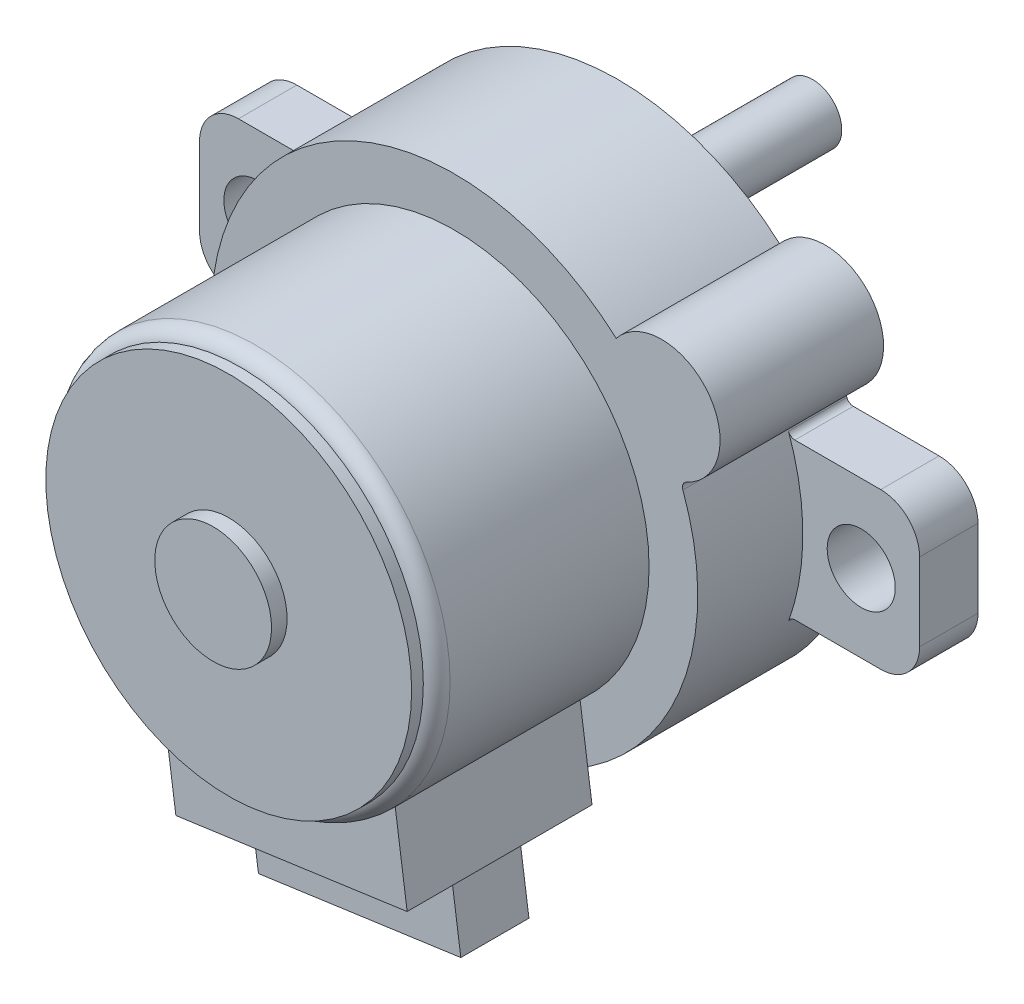
SolidWorks part; units mm, degrees
ref_plane "正面" through (0, 0, 0) normal (0, 0, 1) x (1, 0, 0)
ref_plane "平面" through (0, 0, 0) normal (0, 1, 0) x (1, 0, 0)
ref_plane "右側面" through (0, 0, 0) normal (1, 0, 0) x (0, 0, -1)
sketch "ｽｹｯﾁ1" plane through (0, 0, 0) normal (0, 0, 1) x (1, 0, 0)
  circle A0 centre (0, 0) radius 10
  dimension "D1" = 20
extrude "ﾎﾞｽ - 押し出し1" add sketch "ｽｹｯﾁ1" along normal blind 11.6
sketch "ｽｹｯﾁ2" plane through (0, 0, 0) normal (0, 0, 1) x (1, 0, 0)
  circle A0 centre (0, 0) radius 12.5
  dimension "D1" = 25
extrude "ﾎﾞｽ - 押し出し2" add sketch "ｽｹｯﾁ2" against normal blind 8.4
sketch "ｽｹｯﾁ3" plane through (0, 0, -8.4) normal (0, 0, -1) x (-1, 0, 0)
  line L0 (-28.5789, 0) -> (34.8787, 0) construction
  line L1 (-18.5, 2) -> (-18.5, -2)
  line L2 (-16.5, -4) -> (-11.8427, -4)
  line L3 (-16.5, 4) -> (-11.8427, 4)
  line L4 (0, 0) -> (-18.1375, 12.7) construction
  line L5 (16.5, 4) -> (11.8427, 4)
  line L6 (16.5, -4) -> (11.8427, -4)
  line L7 (18.5, -2) -> (18.5, 2)
  circle A0 centre (-15.5, 0) radius 1.75
  circle A1 centre (0, 0) radius 12.5
  arc A2 (-8.3112, 9.3367) -> (-11.6162, 4.6167) centre (0, 0) ccw
  arc A3 (-8.3112, 9.3367) -> (-11.6162, 4.6167) centre (-10.649, 7.4565) ccw
  arc A4 (-18.5, -2) -> (-16.5, -4) centre (-16.5, -2) ccw
  arc A5 (-18.5, 2) -> (-16.5, 4) centre (-16.5, 2) cw
  arc A6 (-11.8427, 4) -> (-11.8427, -4) centre (0, 0) ccw
  arc A8 (8.3112, -9.3367) -> (11.6162, -4.6167) centre (0, 0) ccw
  arc A9 (8.3112, -9.3367) -> (11.6162, -4.6167) centre (10.649, -7.4565) ccw
  arc A10 (11.8427, -4) -> (11.8427, 4) centre (0, 0) ccw
  arc A11 (18.5, -2) -> (16.5, -4) centre (16.5, -2) cw
  arc A12 (18.5, 2) -> (16.5, 4) centre (16.5, 2) ccw
  circle A13 centre (15.5, 0) radius 1.75
  point P8 (-18.5, 0)
  point P18 (-18.5, -4)
  point P21 (-18.5, 4)
  point P39 (0, 0)
  dimension "D4" = 3.5
  dimension "D5" = 15.5
  dimension "D7" = 6
  dimension "D9" = 2
  dimension "D2" = 8
  dimension "D3" = 18.5
  dimension "D6" = 35
  dimension "D8" = 13
  dimension "D1" = 0
  dimension "D10" = 2
extrude "ﾎﾞｽ - 押し出し3" add sketch "ｽｹｯﾁ3" against normal blind 3
sketch "ｽｹｯﾁ4" plane through (0, 0, -5.4) normal (0, 0, 1) x (1, 0, 0)
  arc A0 (-11.6162, -4.6167) -> (-8.3112, -9.3367) centre (-10.649, -7.4565) ccw construction
  arc A1 (-11.6162, -4.6167) -> (-8.3112, -9.3367) centre (0, 0) ccw construction
  arc A2 (11.6162, 4.6167) -> (8.3112, 9.3367) centre (10.649, 7.4565) ccw construction
  arc A3 (11.6162, 4.6167) -> (8.3112, 9.3367) centre (0, 0) ccw construction
  arc A4 (-11.6162, -4.6167) -> (-8.3112, -9.3367) centre (-10.649, -7.4565) ccw
  arc A5 (-11.6162, -4.6167) -> (-8.3112, -9.3367) centre (0, 0) ccw
  arc A6 (11.6162, 4.6167) -> (8.3112, 9.3367) centre (10.649, 7.4565) ccw
  arc A7 (11.6162, 4.6167) -> (8.3112, 9.3367) centre (0, 0) ccw
extrude "ﾎﾞｽ - 押し出し4" add sketch "ｽｹｯﾁ4" along normal up to surface (5.4 mm away) up to face at (10, 0, 0)
sketch "ｽｹｯﾁ5" plane through (0, 0, -8.4) normal (0, 0, -1) x (-1, 0, 0)
  line L0 (0, 6) -> (0, 0) construction
  circle A0 centre (0, 6) radius 3
  dimension "D1" = 6
  dimension "D2" = 6
extrude "ﾎﾞｽ - 押し出し5" add sketch "ｽｹｯﾁ5" along normal blind 2
sketch "ｽｹｯﾁ6" plane through (0, 0, -10.4) normal (0, 0, -1) x (-1, 0, 0)
  circle A0 centre (0, 6) radius 1.5
  dimension "D1" = 3
extrude "ﾎﾞｽ - 押し出し6" add sketch "ｽｹｯﾁ6" along normal blind 8
sketch "ｽｹｯﾁ7" plane through (0, 0, 11.6) normal (0, 0, 1) x (1, 0, 0)
  circle A0 centre (0, 0) radius 3
  dimension "D1" = 6
extrude "ﾎﾞｽ - 押し出し7" add sketch "ｽｹｯﾁ7" along normal blind 0.8
sketch "ｽｹｯﾁ8" plane through (0, 0, 11.6) normal (0, 0, 1) x (1, 0, 0)
  line L0 (0, 0) -> (2.4461, -17.4049) construction
  line L1 (0, 0) -> (0, -16.419) construction
  line L2 (-4.2159, -13.1144) -> (7.6674, -11.4443)
  line L3 (7.6674, -11.4443) -> (7.055, -7.0871)
  line L4 (-4.8282, -8.7572) -> (-4.2159, -13.1144)
  circle A0 centre (0, 0) radius 3 construction
  circle A1 centre (0, 0) radius 10
  arc A2 (-4.8282, -8.7572) -> (7.055, -7.0871) centre (0, 0) ccw
  point P9 (1.7257, -12.2793)
  dimension "D2" = 8
  dimension "D3" = 12
  dimension "D4" = 12.4
  dimension "D1" = 0
extrude "ﾎﾞｽ - 押し出し8" add sketch "ｽｹｯﾁ8" against normal blind 11
sketch "ｽｹｯﾁ9" plane through (0, 0, 11.6) normal (0, 0, 1) x (1, 0, 0)
  line L0 (-4.8282, -8.7572) -> (-4.2159, -13.1144) construction
  line L1 (-3.4732, -13.01) -> (-2.9721, -16.5749)
  line L2 (-4.2159, -13.1144) -> (7.6674, -11.4443) construction
  line L3 (-2.9721, -16.5749) -> (7.4257, -15.1136)
  line L4 (6.9247, -11.5487) -> (7.4257, -15.1136)
  line L5 (-3.4732, -13.01) -> (6.9247, -11.5487)
  circle A0 centre (0, 0) radius 3 construction
  dimension "D1" = 16
  dimension "D2" = 10.5
  dimension "D3" = 0.75
extrude "ﾎﾞｽ - 押し出し9" add sketch "ｽｹｯﾁ9" against normal blind 8
sketch "ｽｹｯﾁ10" plane through (0, 0, 11.6) normal (0, 0, 1) x (1, 0, 0)
  line L4 (6.9247, -11.5487) -> (-3.4732, -13.01)
  line L5 (7.4257, -15.1136) -> (6.9247, -11.5487)
  line L6 (-2.9721, -16.5749) -> (7.4257, -15.1136)
  line L7 (-3.4732, -13.01) -> (-2.9721, -16.5749)
  line L8 (6.9247, -11.5487) -> (-3.4732, -13.01)
  line L9 (7.4257, -15.1136) -> (6.9247, -11.5487)
  line L10 (-2.9721, -16.5749) -> (7.4257, -15.1136)
  line L11 (-3.4732, -13.01) -> (-2.9721, -16.5749)
  dimension "D1" = 0
extrude "ｶｯﾄ - 押し出し1" cut sketch "ｽｹｯﾁ10" against normal blind 4.5
fillet "ﾌｨﾚｯﾄ1" radius 0.5 4 edges at (6.9247, -11.5487, 5.35) (1.7257, -12.2793, 7.1) (1.7257, -12.2793, 3.6) (-3.4732, -13.01, 5.35)
fillet "ﾌｨﾚｯﾄ4" radius 0.35 6 edges at (11.8427, 4, -6.9) (11.6162, 4.6167, -4.2) (-11.6162, -4.6167, -4.2) (-11.8427, -4, -6.9) (11.8427, -4, -6.9) (-11.8427, 4, -6.9)
sketch "ｽｹｯﾁ11" plane through (0, 0, 11.6) normal (0, 0, 1) x (1, 0, 0)
  line L3 (-4.8282, -8.7572) -> (-4.2159, -13.1144)
  line L4 (7.6674, -11.4443) -> (7.055, -7.0871)
  line L5 (-4.2159, -13.1144) -> (7.6674, -11.4443)
  line L6 (-4.8282, -8.7572) -> (-4.2159, -13.1144)
  line L7 (7.6674, -11.4443) -> (7.055, -7.0871)
  line L8 (-4.2159, -13.1144) -> (7.6674, -11.4443)
  arc A1 (-4.8282, -8.7572) -> (7.055, -7.0871) centre (0, 0) ccw
  arc A2 (-4.8282, -8.7572) -> (7.055, -7.0871) centre (0, 0) ccw
  dimension "D1" = 0
extrude "ｶｯﾄ - 押し出し2" cut sketch "ｽｹｯﾁ11" against normal blind 1.5
sketch "ｽｹｯﾁ12" plane through (0, 0, 11.6) normal (0, 0, 1) x (1, 0, 0)
  circle A0 centre (0, 0) radius 9.4
  circle A1 centre (0, 0) radius 10
  circle A2 centre (0, 0) radius 10
  dimension "D1" = 0
  dimension "D2" = 0.6
extrude "ｶｯﾄ - 押し出し3" cut sketch "ｽｹｯﾁ12" against normal blind 0.6
fillet "ﾌｨﾚｯﾄ5" radius 0.8 1 edges at (10, 0, 11)
